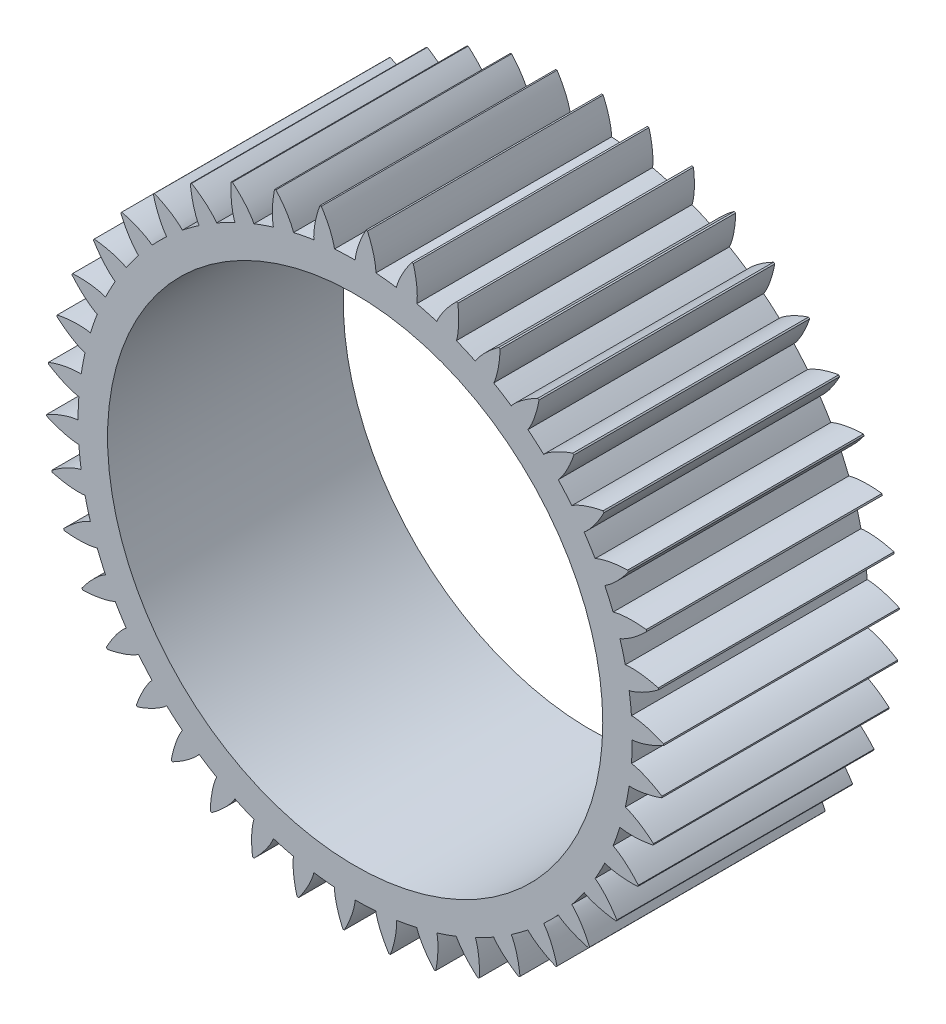
SolidWorks part; units mm, degrees
ref_plane "Front Plane" through (0, 0, 0) normal (0, 0, 1) x (1, 0, 0)
ref_plane "Top Plane" through (0, 0, 0) normal (0, 1, 0) x (1, 0, 0)
ref_plane "Right Plane" through (0, 0, 0) normal (1, 0, 0) x (0, 0, -1)
sketch "Sketch1" plane through (0, 0, 0) normal (0, 0, 1) x (1, 0, 0)
  line L0 (0, 0) -> (52.3443, -1.9586) construction
  line L1 (0, 0) -> (52.3443, 1.9586) construction
  line L2 (0, 0) -> (52.3443, -1.9586) construction
  line L3 (0, 0) -> (52.381, 0) construction
  line L4 (0, 0) -> (52.0516, 5.8648) construction
  line L5 (41.9944, 1.5713) -> (52.3443, 1.9586)
  line L6 (41.9944, -1.5713) -> (46.9909, -1.7583)
  line L7 (46.9846, 0) -> (48.983, 0)
  circle A0 centre (0, 0) radius 50 construction
  circle A1 centre (0, 0) radius 47.0238 construction
  circle A2 centre (0, 0) radius 46.9846 construction
  circle A3 centre (0, 0) radius 52.381 construction
  arc A4 (41.9944, 1.5713) -> (41.9944, -1.5713) centre (0, 0) cw
  arc A5 (46.9847, -1.9184) -> (46.9909, -1.7583) centre (0, 0) cw
  arc A6 (52.3443, 1.9586) -> (52.349, 1.8297) centre (0, 0) cw
  spline S0 degree 4 poles (46.9846, 0) (47.0467, 0.0018) (47.1706, 0.0089) (47.4054, 0.0347) (47.7494, 0.0889) (48.3388, 0.21) (49.2603, 0.4646) (50.4706, 0.9041) (52.1042, 1.6596) (53.9325, 2.7102) (55.836, 4.0308) (57.7649, 5.6167) (59.5726, 7.3388) (61.2614, 9.1774) (62.9111, 11.2123) (64.7951, 13.8529) (66.7982, 17.1643) (68.785, 21.1974) (70.5742, 25.8619) (71.9606, 30.6607) (72.96, 35.5541) (73.5094, 39.8891) (73.7576, 43.6247) (73.8205, 46.743) (73.7863, 49.2381) (73.6695, 51.7304) (73.4717, 54.2178) (73.1257, 57.3172) (72.6504, 60.4009) (72.1108, 63.1551) (71.5463, 65.5867) (71.2166, 66.8909) (71.004, 67.6932) (70.8205, 68.3656) (70.621, 69.0756) (70.4517, 69.6602) (70.1201, 70.7707) (69.855, 71.6065) (69.5211, 72.6398) (69.212, 73.5456) (68.8694, 74.527) (68.5321, 75.4491) (68.2609, 76.1741) (68.0833, 76.6328) (67.9907, 76.8718) knots 0 0 0 0 0 0.002802 0.005604 0.010661 0.015718 0.02996 0.048734 0.068727 0.096889 0.125051 0.153212 0.181374 0.209535 0.237696 0.271429 0.327752 0.384075 0.440398 0.496721 0.553044 0.609367 0.637529 0.66569 0.693852 0.722013 0.750174 0.778336 0.834659 0.86282 0.876901 0.890982 0.895509 0.900036 0.909091 0.920455 0.931818 0.943182 0.954545 0.965909 0.977273 0.988636 1 1 1 1 1 construction
  spline S1 degree 4 poles (46.9846, 0) (47.0467, 0.0018) (47.1706, 0.0089) (47.4054, 0.0347) (47.7494, 0.0889) (48.3388, 0.21) (49.2603, 0.4646) (50.4706, 0.9041) (52.1042, 1.6596) (53.9325, 2.7102) (55.836, 4.0308) (57.7649, 5.6167) (59.5726, 7.3388) (61.2614, 9.1774) (62.9111, 11.2123) (64.7951, 13.8529) (66.7982, 17.1643) (68.785, 21.1974) (70.5742, 25.8619) (71.9606, 30.6607) (72.96, 35.5541) (73.5094, 39.8891) (73.7576, 43.6247) (73.8205, 46.743) (73.7863, 49.2381) (73.6695, 51.7304) (73.4717, 54.2178) (73.1257, 57.3172) (72.6504, 60.4009) (72.1108, 63.1551) (71.5463, 65.5867) (71.2166, 66.8909) (71.004, 67.6932) (70.8205, 68.3656) (70.6979, 68.8018) (70.6215, 69.0699) (70.571, 69.2451) knots 0 0 0 0 0 0.002802 0.005604 0.010661 0.015718 0.02996 0.048734 0.068727 0.096889 0.125051 0.153212 0.181374 0.209535 0.237696 0.271429 0.327752 0.384075 0.440398 0.496721 0.553044 0.609367 0.637529 0.66569 0.693852 0.722013 0.750174 0.778336 0.834659 0.86282 0.876901 0.890982 0.895509 0.900036 0.909091 0.909091 0.909091 0.909091 0.909091
  point P10 (46.9909, 1.7583)
  point P21 (47.0238, 0)
  dimension "pitchRadius" = 50
  dimension "addendumRadius" = 52.381
  dimension "dedendumRadius" = 47.0238
  dimension "baseRadius" = 46.9846
  dimension "D1" = 4.286
  dimension "D2" = 2.143
  dimension "toothArc" = 8.571
  dimension "D3" = 5
extrude "Boss-Extrude1" add sketch "Sketch1" along normal blind 40 contours S1 A6 L5 | L7 S1 A5 L5 A4 L6 region at (44.5602, 0, 0) region at (49.0288, 1.1619, 0)
mirror "Mirror1" about plane through (0, 0, 40) normal (-0.0374, 0.9993, 0) of "Boss-Extrude1"
pattern_circular "CirPattern1" count 42 over 360 about axis through (0, 0, 40) along (0, 0, -1) of "Boss-Extrude1", "Mirror1"
equation "\"D1@Sketch1\"=\"toothArc@Sketch1\"/2"
equation "\"D2@Sketch1\"=\"toothArc@Sketch1\"/4"
equation "\"pitchRadius\"= 5"
equation "\"nTeeth\"= 42"
equation "\"pressureAngle\"= 20"
equation "\"baseRadius\"= \"pitchRadius\" * cos ( \"pressureAngle\" )"
equation "\"diametralPitch\"= \"nTeeth\" / ( 2 * \"pitchRadius\" )'note units: cm^-1"
equation "\"dedendum\"= 1.25 / \"diametralPitch\"'for full depth, 20 deg pressure angle"
equation "\"addendum\"= 1 / \"diametralPitch\""
equation "\"pitchRadius@Sketch1\"= \"pitchRadius\""
equation "\"addendumRadius@Sketch1\"= \"pitchRadius\" + \"addendum\""
equation "\"dedendumRadius@Sketch1\"= \"pitchRadius\" - \"dedendum\""
equation "\"baseRadius@Sketch1\"= \"baseRadius\""
equation "\"toothArc@Sketch1\"=360/\"nTeeth\""
equation "\"D1@CirPattern1\"=\"nTeeth\""
